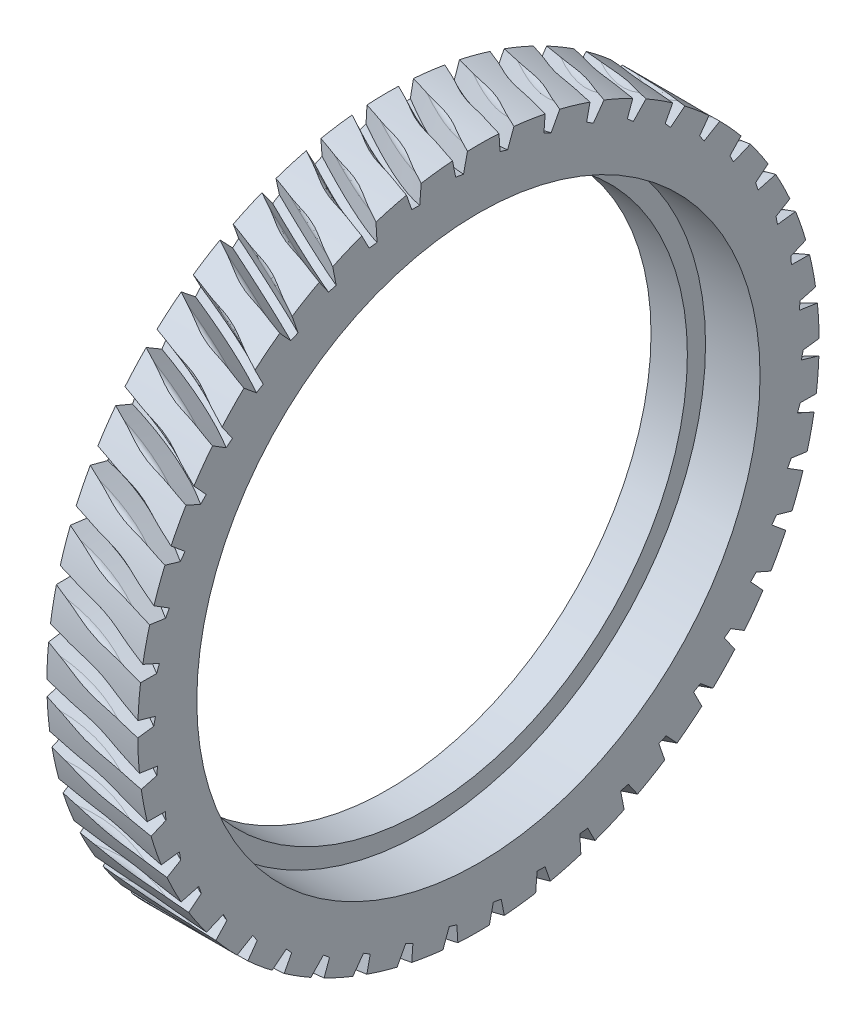
SolidWorks part; units mm, degrees
ref_plane "Plane1" through (0, 0, 0) normal (0, 0, 1) x (1, 0, 0)
ref_plane "Plane2" through (0, 0, 0) normal (0, 1, 0) x (1, 0, 0)
ref_plane "Plane3" through (0, 0, 0) normal (1, 0, 0) x (0, 0, -1)
sketch "Esquisse1" plane through (0, 0, 0) normal (0, 0, 1) x (1, 0, 0)
  line L0 (0, 31) -> (0, 37.5)
  line L1 (0, 37.5) -> (-10, 37.5)
  line L2 (-10, 37.5) -> (-10, 29)
  line L3 (-10, 29) -> (-6, 29)
  line L4 (-6, 29) -> (-6, 31)
  line L5 (-6, 31) -> (0, 31)
  line L6 (0, 0) -> (17, 0) construction
  line L7 (-5, 0) -> (-5, 50) construction
  dimension "D1" = 37.5
  dimension "D2" = 31
  dimension "D3" = 29
  dimension "D4" = 6
  dimension "D5" = 10
  dimension "D6" = 5
revolve "Base-Révolution" add sketch "Esquisse1" angle 360 about L6
sketch "Esquisse2" plane through (0, 0, 0) normal (0, 0, 1) x (1, 0, 0)
  line L0 (-5, 0) -> (-5, 20) construction
  dimension "D1" = 5
ref_plane "Plan6" through (-0.7322, 0, 1.7678) normal (0.3827, 0, -0.9239) x (-0.9239, 0, -0.3827)
ref_plane "Plan7" through (-4.2678, 0, -1.7678) normal (-0.9239, 0, -0.3827) x (-0.3827, 0, 0.9239)
sketch "Esquisse4" plane through (-4.2678, 0, -1.7678) normal (-0.9239, 0, -0.3827) x (-0.3827, 0, 0.9239)
  line L0 (-13.9, 48.5) -> (25.1, 48.5) construction
  line L1 (1.0016, 36.9079) -> (1.5134, 34.5)
  line L2 (1.5134, 34.5) -> (2.3134, 34.5)
  line L3 (1.9134, 0) -> (1.9134, 16.5056) construction
  line L4 (1.9134, 19.1595) -> (1.9134, -19.1595) construction
  line L5 (2.8252, 36.9079) -> (2.3134, 34.5)
  line L6 (-3.9, 37.7) -> (-3.9, 39.7)
  line L7 (-3.9, 37.7) -> (0.0235, 37.7)
  line L8 (8.1, 37.7) -> (3.8034, 37.7)
  line L9 (-3.9, 39.7) -> (8.1, 39.7)
  line L10 (8.1, 39.7) -> (8.1, 37.7)
  line L11 (1.9134, 34.5) -> (1.9134, 44.8852) construction
  arc A0 (1.0016, 36.9079) -> (0.0235, 37.7) centre (0.0235, 36.7) ccw
  arc A1 (3.8034, 37.7) -> (2.8252, 36.9079) centre (3.8034, 36.7) ccw
  dimension "D1" = 0.8
  dimension "D3" = 34.5
  dimension "D5" = 3.2
  dimension "D6" = 2
  dimension "D7" = 14
  dimension "D8" = 12
  dimension "D9" = 12
revolve "Enlever de la matière-Révolution1" cut sketch "Esquisse4" angle 360 about L0
pattern_circular "Répétition circulaire1" count 46 every 7.826 about axis through (0, 0, 0) along (1, 0, 0) of "Enlever de la matière-Révolution1"
